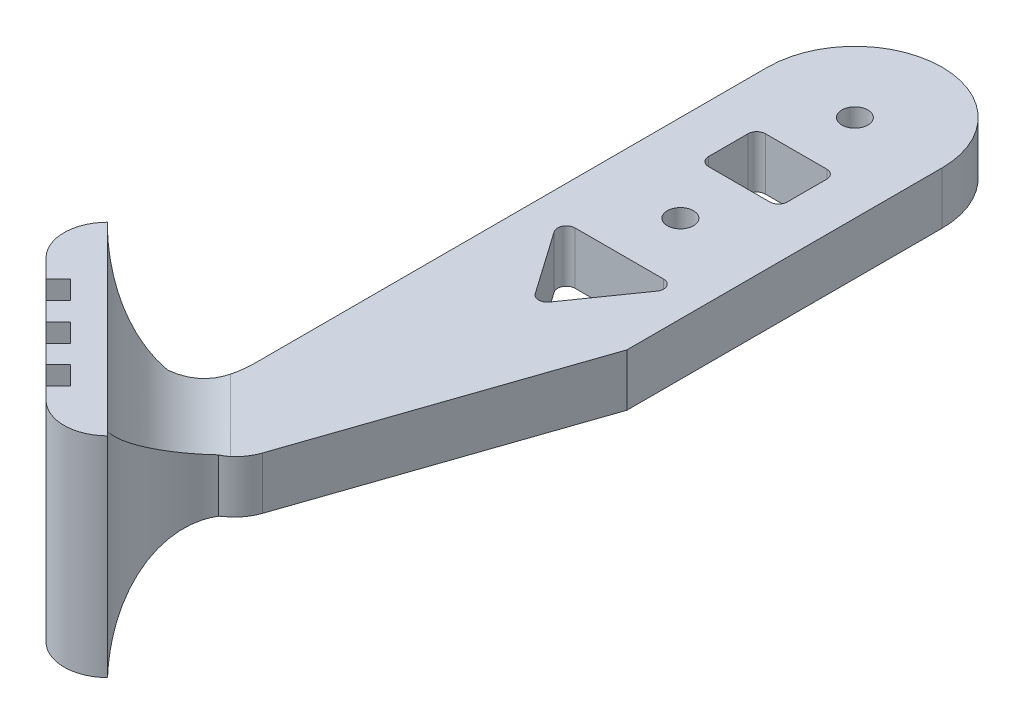
SolidWorks part; units mm, degrees
ref_plane "Front Plane" through (0, 0, 0) normal (0, 0, 1) x (1, 0, 0)
ref_plane "Top Plane" through (0, 0, 0) normal (0, 1, 0) x (1, 0, 0)
ref_plane "Right Plane" through (0, 0, 0) normal (1, 0, 0) x (0, 0, -1)
sketch "Sketch1" plane through (0, 0, 0) normal (0, 1, 0) x (1, 0, 0)
  line L0 (0, 0) -> (0, 20) construction
  line L1 (0, 20) -> (0, 30) construction
  line L2 (0, 0) -> (0, -30) construction
  line L3 (-10, 20) -> (-10, -100)
  line L4 (10, 20) -> (10, -100)
  line L5 (10, -100) -> (-10, -100)
  circle A0 centre (0, 0) radius 1.5
  circle A1 centre (0, 20) radius 1.5
  arc A2 (10, 20) -> (-10, 20) centre (0, 20) ccw
  dimension "D1" = 20
  dimension "D2" = 10
  dimension "D3" = 30
extrude "Boss-Extrude1" add sketch "Sketch1" along normal blind 6 contours A0 | A1 | L4 L5 L3 A2 region at (0, 0, 0) region at (0, 0, -20)
sketch "Sketch3" plane through (0, 6, 0) normal (0, 1, 0) x (1, 0, 0)
  line L0 (0, 0) -> (0, -7) construction
  line L1 (7, -7) -> (-7, -7)
  line L2 (0, -7) -> (0, -17) construction
  line L3 (-7, -7) -> (0, -17)
  line L4 (7, -7) -> (0, -17)
  line L5 (0, -17) -> (0, -22) construction
  line L6 (0, -22) -> (0, -52) construction
  line L10 (0, -52) -> (0, -62) construction
  line L11 (0, -62) -> (0, -85) construction
  line L12 (6.5, -85) -> (-6.5, -85) construction
  line L13 (6.5, -62) -> (-6.5, -62)
  line L14 (-6.5, -62) -> (-6.5, -85)
  line L15 (6.5, -62) -> (6.5, -85)
  line L16 (-6.5, -85) -> (6.5, -85)
  line L17 (0, 0) -> (0, 20) construction
  line L19 (-4.5136, 6.7359) -> (4.5136, 6.7359)
  line L20 (-4.5136, 6.7359) -> (-4.5136, 13.2641)
  line L21 (-4.5136, 13.2641) -> (4.5136, 13.2641)
  line L22 (4.5136, 6.7359) -> (4.5136, 13.2641)
  line L23 (-4.5136, 6.7359) -> (4.5136, 13.2641) construction
  line L24 (-4.5136, 13.2641) -> (4.5136, 6.7359) construction
  point P16 (0, 10)
  dimension "D1" = 7
  dimension "D2" = 7
  dimension "D3" = 10
  dimension "D4" = 5
  dimension "D5" = 30
  dimension "D6" = 10
  dimension "D7" = 23
extrude "Cut-Extrude1" cut sketch "Sketch3" against normal blind 14 contours L16 L15 L13 L14 | L4 L3 L1 | L20 L19 L22 L21
fillet "Fillet1" radius 1 11 edges at (-6.5, 3, 85) (-6.5, 3, 62) (6.5, 3, 62) (6.5, 3, 85) (-7, 3, 7) (7, 3, 7) (0, 3, 17) (4.5136, 3, -6.7359) (-4.5136, 3, -6.7359) (4.5136, 3, -13.2641) (-4.5136, 3, -13.2641)
sketch "Sketch13" plane through (0, 0, 0) normal (0, -1, 0) x (1, 0, 0)
  line L0 (0, 0) -> (0, 80) construction
  line L1 (0, 80) -> (14.1421, 94.1421) construction
  line L2 (0, 80) -> (-15.569, 64.431)
  line L3 (-15.569, 64.431) -> (-15.569, 115.4929)
  line L4 (-15.569, 115.4929) -> (18.2125, 115.4929)
  line L5 (18.2125, 115.4929) -> (14.1421, 94.1421)
  line L6 (14.1421, 94.1421) -> (-15.569, 64.431)
  arc M17 (-6.5, 94) -> (-5.5, 95) centre (-5.5, 94) cw
  line M18 (-5.5, 95) -> (-9.5394, 95)
  line M19 (-9.5394, 95) -> (-9.5394, 100)
  line M20 (-9.5394, 100) -> (-10, 100)
  line M21 (-10, 100) -> (-10, -20)
  line M27 (10, 85) -> (10, 100)
  line M28 (10, 100) -> (9.5394, 100)
  line M29 (9.5394, 100) -> (9.5394, 95)
  line M30 (9.5394, 95) -> (5.5, 95)
  arc M31 (5.5, 95) -> (6.5, 94) centre (5.5, 94) cw
  line M32 (6.5, 94) -> (6.5, 73)
  line M36 (-6.5, 73) -> (-6.5, 94)
  dimension "D1" = 80
  dimension "D2" = 20
extrude "Cut-Extrude8" cut sketch "Sketch13" against normal blind 20 and the other way blind 20 contours L6 L5 L4 L3 L2 M21 M20 M19 M18 M17 M36 M32 M31 M30 M29 M28 M27 region at (-1.7797, 0, 98.0491)
sketch "Sketch16" plane through (0, 6, 0) normal (0, 1, 0) x (1, 0, 0)
  line L1 (33.3965, -104.0829) -> (-32.3606, -104.0829)
  line L2 (33.3965, -104.0829) -> (33.3965, -25.8208)
  line L3 (33.3965, -25.8208) -> (-32.3606, -25.8208)
  line L4 (-32.3606, -104.0829) -> (-32.3606, -25.8208)
extrude "Cut-Extrude10" cut sketch "Sketch16" against normal blind 10
sketch "Sketch17" plane through (0, 6, 0) normal (0, 1, 0) x (1, 0, 0)
  line L0 (0, 0) -> (0, -50) construction
  line L1 (10, -25.8208) -> (10, -50) construction
  line L2 (10, -50) -> (0, -50) construction
  line L4 (10, -50) -> (-10, -50)
  line L5 (10, -50) -> (10, -25.8208)
  line L6 (10, -25.8208) -> (-10, -25.8208)
  line L7 (-10, -50) -> (-10, -25.8208)
  dimension "D1" = 50
extrude "Boss-Extrude2" add sketch "Sketch17" against normal blind 6 contours L5 L4 L7 L6
sketch "Sketch18" plane through (0, 6, 0) normal (0, 1, 0) x (1, 0, 0)
  line L0 (-10, -50) -> (10, -50) construction
  line L1 (-10, -50) -> (-13.5355, -53.5355) construction
  line L2 (-13.5355, -53.5355) -> (-10, -57.0711) construction
  line L3 (-13.5355, -53.5355) -> (-17.0711, -50) construction
  line L4 (-17.0711, -50) -> (-10, -42.9289)
  line L5 (-10, 20) -> (-10, -50) construction
  line L6 (-10, -57.0711) -> (-2.9289, -50)
  line L7 (-10, -57.0711) -> (-6.4645, -60.6066)
  line L8 (-17.0711, -50) -> (-20.6066, -46.4645)
  line L9 (-20.6066, -46.4645) -> (-23.435, -49.2929)
  line L10 (-6.4645, -60.6066) -> (-10.5364, -64.6786) construction
  line L11 (-23.435, -49.2929) -> (-9.2929, -63.435)
  line L12 (-6.4645, -60.6066) -> (-9.2929, -63.435)
  line L13 (-10, -42.9289) -> (-10, -50)
  line L14 (-10, -50) -> (-2.9289, -50)
  dimension "D1" = 135
  dimension "D2" = 5
  dimension "D3" = 5
  dimension "D4" = 5
  dimension "D5" = 5
  dimension "D6" = 5
  dimension "D7" = 4
extrude "Boss-Extrude3" add sketch "Sketch18" against normal blind 6
sketch "Sketch19" plane through (-36.364, 0, 36.364) normal (-0.7071, 0, 0.7071) x (0.7071, 0, 0.7071)
  line L0 (18.2843, 3) -> (18.2843, 15) construction
  line L1 (18.2843, 0) -> (18.2843, 6) construction
  line L2 (38.2843, 3) -> (38.2843, -9) construction
  line L3 (38.2843, 0) -> (38.2843, 6) construction
  line L5 (18.2843, 15) -> (38.2843, 15)
  line L6 (18.2843, 15) -> (18.2843, -9)
  line L7 (18.2843, -9) -> (38.2843, -9)
  line L8 (38.2843, 15) -> (38.2843, -9)
  dimension "D1" = 12
  dimension "D2" = 12
  dimension "D3" = 20
extrude "Boss-Extrude5" add sketch "Sketch19" against normal blind 5 contours L6 L5 L8 L7
sketch "Sketch20" plane through (-36.364, 0, 36.364) normal (-0.7071, 0, 0.7071) x (0.7071, 0, 0.7071)
  line L0 (18.2843, -9) -> (38.2843, 15) construction
  line L1 (38.2843, 15) -> (28.2843, 3) construction
  line L2 (28.2843, 3) -> (28.2843, 15) construction
  line L3 (18.2843, 15) -> (38.2843, 15) construction
  line L4 (28.2843, 15) -> (13.2843, 15) construction
  line L5 (28.2843, 3) -> (28.2843, -9) construction
  line L6 (18.2843, -9) -> (38.2843, -9) construction
  line L7 (28.2843, -9) -> (43.2843, -9) construction
  line L9 (13.2843, 15) -> (43.2843, 15)
  line L10 (13.2843, 15) -> (13.2843, -9)
  line L11 (13.2843, -9) -> (43.2843, -9)
  line L12 (43.2843, 15) -> (43.2843, -9)
  dimension "D1" = 15
  dimension "D2" = 15
extrude "Boss-Extrude6" add sketch "Sketch20" against normal blind 5 contours L10 L9 L12 L11
fillet "Fillet2" radius 5 2 edges at (-5.7574, 3, 66.9706) (-26.9706, 3, 45.7574)
fillet "Fillet3" radius 10 1 edges at (-10, 3, 42.9289)
fillet "Fillet4" radius 10 4 edges at (-12.8284, 0, 52.8284) (-9.2929, 3, 56.364) (-16.364, 3, 49.2929) (-12.8284, 6, 52.8284)
sketch "Sketch21" plane through (0, 6, 0) normal (0, 1, 0) x (1, 0, 0)
  line L0 (-1.5856, -50) -> (10, -16.1292)
  line L1 (10, 20) -> (10, -50) construction
  line L2 (10, -16.1292) -> (10, -50)
  line L3 (10, -50) -> (-1.5856, -50)
  point P7 (-1.5856, -50)
  point P8 (-1.5856, -50)
  point P9 (0, 0)
extrude "Cut-Extrude11" cut sketch "Sketch21" against normal blind 12
fillet "Fillet6" radius 5 1 edges at (-1.5856, 3, 50)
sketch "Sketch22" plane through (-36.364, 0, 36.364) normal (-0.7071, 0, 0.7071) x (0.7071, 0, 0.7071)
  line L0 (18.2843, 15) -> (21.2843, 15) construction
  line L1 (18.2843, 15) -> (38.2843, 15) construction
  line L2 (18.2843, -9) -> (38.2843, -9) construction
  line L3 (21.2843, 15) -> (24.2843, 15)
  line L4 (21.2843, 15) -> (21.2843, -9)
  line L5 (21.2843, -9) -> (24.2843, -9)
  line L6 (24.2843, 15) -> (24.2843, -9)
  line L7 (27.2843, 15) -> (27.2843, -9)
  line L8 (27.2843, 15) -> (30.2843, 15)
  line L9 (30.2843, 15) -> (30.2843, -9)
  line L10 (27.2843, -9) -> (30.2843, -9)
  line L11 (33.2843, 15) -> (33.2843, -9)
  line L12 (33.2843, 15) -> (36.2843, 15)
  line L13 (36.2843, 15) -> (36.2843, -9)
  line L14 (33.2843, -9) -> (36.2843, -9)
  dimension "D1" = 3
  dimension "D2" = 3
  dimension "D3" = 3
extrude "Cut-Extrude12" cut sketch "Sketch22" against normal blind 2
